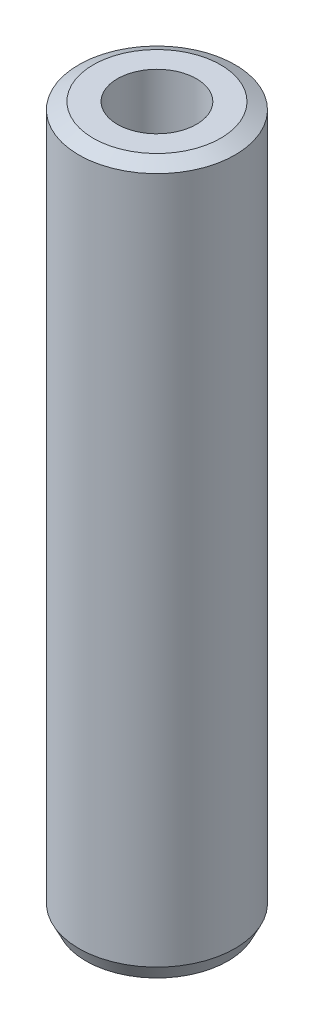
SolidWorks part; units mm, degrees
ref_plane "Front Plane" through (0, 0, 0) normal (0, 0, 1) x (1, 0, 0)
ref_plane "Top Plane" through (0, 0, 0) normal (0, 1, 0) x (1, 0, 0)
ref_plane "Right Plane" through (0, 0, 0) normal (1, 0, 0) x (0, 0, -1)
sketch "Sketch1" plane through (0, 0, 0) normal (0, 1, 0) x (1, 0, 0)
  circle A0 centre (0, 0) radius 47.5
  dimension "SHAFT_OD" = 95
extrude "Boss-Extrude1" add sketch "Sketch1" along normal blind 430.6625
sketch "Sketch2" plane through (0, 0, 0) normal (0, 1, 0) x (1, 0, 0)
  circle A0 centre (0, 0) radius 24.0243
  dimension "BORE_D" = 48.0485
extrude "Cut-Extrude1" cut sketch "Sketch2" along normal through all
chamfer "Chamfer1" distance 4.3686 angle 63.619 2 edges at (0, 430.6625, 47.5) (0, 0, 47.5) first distance on face at (0, 430.6625, 47.5) first distance on face at (0, 0, 24.0243)
